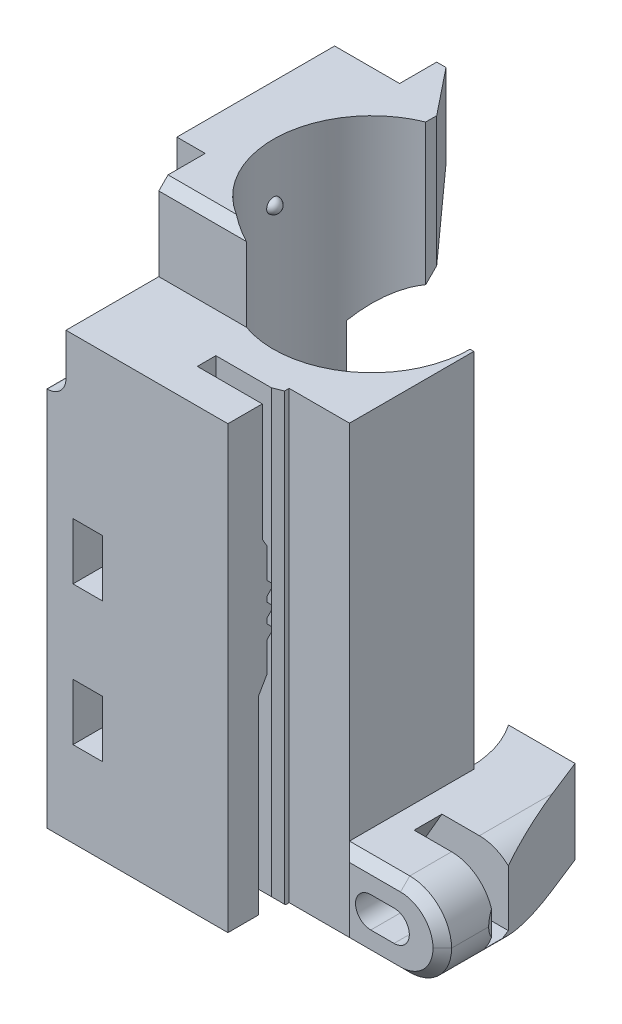
SolidWorks part; units mm, degrees
material "Custom Plastic"
ref_plane "Front Plane" through (0, 0, 0) normal (0, 0, 1) x (1, 0, 0)
ref_plane "Top Plane" through (0, 0, 0) normal (0, 1, 0) x (1, 0, 0)
ref_plane "Right Plane" through (0, 0, 0) normal (1, 0, 0) x (0, 0, -1)
sketch "Sketch2" plane through (0, 0, 0) normal (0, 1, 0) x (1, 0, 0)
  line L0 (22, -14.4) -> (22, -9.4)
  line L1 (16, 6) -> (16, -12.9) construction
  line L2 (11, -13.4) -> (4.5, -13.4)
  line L3 (4.5, -13.4) -> (4.5, -20)
  line L4 (4.5, -20) -> (-15, -20)
  line L5 (-15, -20) -> (-15, 16)
  line L6 (22, -9.4) -> (14.1647, -9.4) construction
  line L7 (8.7384, 6) -> (15.906, 6)
  line L8 (-15, 16) -> (-4, 16)
  line L9 (-4, 16) -> (-4, 9.8163)
  line L10 (11, -13.4) -> (12, -14.4)
  line L11 (12, -14.4) -> (22, -14.4)
  line L12 (22, -9.4) -> (15.906, 6)
  circle A0 centre (0, 0) radius 10.5 construction
  arc A1 (-4, 9.8163) -> (8.7384, 6) centre (0, 0) ccw
  arc A3 (14.1647, -9.4) -> (15.906, 6) centre (0, 0) ccw construction
  dimension "D1" = 21
  dimension "D2" = 0.1
  dimension "D11" = 17
  dimension "D3" = 4.5
  dimension "D4" = 16
  dimension "D5" = 15
  dimension "D6" = 13.4
  dimension "D7" = 20
  dimension "D8" = 16
  dimension "D9" = 4
  dimension "D10" = 6
  dimension "D12" = 22
  dimension "D14" = 45
  dimension "D15" = 11
  dimension "D16" = 1
extrude "Boss-Extrude1" add sketch "Sketch2" along normal blind 37 and the other way blind 20
sketch "Sketch3" plane through (0, 0, 0) normal (0, -1, 0) x (1, 0, 0)
  circle A0 centre (0, 0) radius 10.5
  dimension "D1" = 21
extrude "Cut-Extrude1" [suppressed] cut sketch "Sketch3" against normal blind 20 from offset 4 offset against normal yes
mirror "Mirror1" [suppressed] about plane through (0, 0, 0) normal (0, 1, 0)
sketch "Sketch4" plane through (0, 37, 0) normal (0, -1, 0) x (1, 0, 0)
  line L0 (4.5, 20) -> (4.5, 13.4) construction
  line L1 (-15, 20) -> (4.5, 20)
  line L2 (-15, 20) -> (-15, 9.9962)
  line L3 (-15, 9.9962) -> (4.5, 9.9962)
  line L4 (4.5, 20) -> (4.5, 9.9962)
extrude "Cut-Extrude3" [suppressed] cut sketch "Sketch4" along normal blind 11
sketch "Sketch5" plane through (4.5, 0, 0) normal (1, 0, 0) x (0, 0, -1)
  line L0 (-15.8, 5.718) -> (-15.3, 6.218)
  line L1 (-14.3, -20) -> (-16.3, -20)
  line L2 (-14.3, -20) -> (-14.3, 37)
  line L3 (-16.3, 37) -> (-14.3, 37)
  line L4 (-15.8, 2.5) -> (-15.8, 5.718)
  line L5 (-15.3, 6.218) -> (-15.3, 6.718)
  line L6 (-15.3, 6.718) -> (-15.8, 7.218)
  line L7 (-15.8, 9.782) -> (-15.3, 10.282)
  line L8 (-15.3, 10.282) -> (-15.3, 10.782)
  line L9 (-15.3, 10.782) -> (-15.8, 11.282)
  line L10 (-15.8, 7.75) -> (-15.3, 8.25)
  line L11 (-15.3, 8.25) -> (-15.3, 8.75)
  line L12 (-15.3, 8.75) -> (-15.8, 9.25)
  line L13 (-15.8, 9.25) -> (-15.8, 9.782)
  line L14 (-15.8, 2.5) -> (-16.3, 1.634)
  line L15 (-15.8, 7.218) -> (-15.8, 7.75)
  line L16 (-16.3, 1.634) -> (-16.3, -20)
  line L17 (-15.8, 11.282) -> (-15.8, 14.5)
  line L18 (-15.8, 14.5) -> (-16.3, 15.366)
  line L19 (-20, -20) -> (-13.4, -20) construction
  line L20 (16, 8.5) -> (-15.3, 8.5) construction
  line L21 (-16.3, 15.366) -> (-16.3, 37)
  line L22 (-20, 37) -> (-13.4, 37) construction
  line L23 (16, -20) -> (16, 37) construction
  dimension "D1" = 0.5
  dimension "D2" = 0.5
  dimension "D3" = 2.032
  dimension "D4" = 1.5
  dimension "D5" = 2
  dimension "D6" = 14.3
  dimension "D7" = 6
  dimension "D8" = 150
extrude "Cut-Extrude5" cut sketch "Sketch5" against normal blind 7
chamfer "Chamfer1" [suppressed] distance 1.2 angle 45
chamfer "Chamfer3" distance 0.5 angle 45 9 edges at (1, -20, 14.3) (-3.0421, -20, 10.1541) (-4, -20, -12.9082) (-9.5, -20, -16) (-15, -20, 2) (-5.25, -20, 20) (4.5, -20, 18.15) (1, -20, 16.3) (-2.5, -20, 15.3)
sketch "Sketch6" plane through (-15, 0, 0) normal (-1, 0, 0) x (0, 0, 1)
  line L0 (13, 7.5) -> (13, -7.5) construction
  line L1 (0, 0) -> (13, 0) construction
  circle A0 centre (13, 7.5) radius 1.55
  circle A1 centre (13, -7.5) radius 1.55
  dimension "D2" = 3.1
  dimension "D1" = 15
  dimension "D3" = 13
extrude "Cut-Extrude6" cut sketch "Sketch6" against normal blind 10
sketch "Sketch7" plane through (-15, 0, 0) normal (-1, 0, 0) x (0, 0, 1)
  line L0 (21.3141, -4.2) -> (21.3141, -10.3)
  line L1 (9.3668, -7.5) -> (10.9834, -10.3)
  line L2 (10.9834, -10.3) -> (21.3141, -10.3)
  line L3 (11.3834, 4.7) -> (9.7668, 7.5)
  line L4 (21.3141, 4.7) -> (11.3834, 4.7)
  line L5 (21.3141, -4.7) -> (11.3834, -4.7) construction
  line L6 (11.2721, -4.2) -> (9.3668, -7.5)
  line L7 (-3, 8.5) -> (19.4531, 8.5) construction
  line L8 (11.2721, -4.2) -> (21.3141, -4.2)
  line L9 (11.3834, 10.3) -> (21.7141, 10.3) construction
  line L10 (13.1374, -12.1691) -> (15.0359, -8.8809) construction
  line L11 (16.6078, -8.8418) -> (15.5516, -7.0123) construction
  line L12 (9.7668, 7.5) -> (11.6721, 10.8)
  line L13 (21.3141, 4.7) -> (21.3141, 10.8)
  line L14 (11.6721, 10.8) -> (21.3141, 10.8)
  circle A0 centre (12.6, -7.5) radius 2.8 construction
  circle A2 centre (13, 7.5) radius 2.8 construction
  circle A3 centre (13, 7.5) radius 1.55 construction
  point P4 (13, -7.5)
  dimension "D1" = 5.6
  dimension "D2" = 0.4
  dimension "D3" = 0.5
  dimension "D4" = 0.5
extrude "Cut-Extrude7" cut sketch "Sketch7" against normal blind 3.2 from offset 2.8 offset against normal yes
sketch "Sketch9" plane through (-15, 0, 0) normal (-1, 0, 0) x (0, 0, 1)
  line L0 (-16, 28) -> (-6, 18)
  line L1 (-16, -19.5) -> (-16, 37) construction
  line L2 (-6, 18) -> (-6, -20)
  line L3 (-16, -20) -> (20, -20) construction
  line L4 (-6, -20) -> (-16, -20)
  line L5 (-16, -20) -> (-16, 28)
  line L6 (-16, 37) -> (20, 37) construction
  dimension "D1" = 9
  dimension "D2" = 6
  dimension "D3" = 45
extrude "Cut-Extrude9" cut sketch "Sketch9" against normal blind 12 and the other way blind 10
sketch "Sketch12" plane through (-15, 0, 0) normal (-1, 0, 0) x (0, 0, 1)
  line L0 (8, 37) -> (8, 30)
  line L1 (-16, 37) -> (20, 37) construction
  line L2 (5, 25) -> (-13, 25)
  line L3 (-16, 28) -> (-13, 25)
  line L4 (-16, 28) -> (-6, 18) construction
  line L5 (-16, 28) -> (-16, 37)
  line L6 (-16, 37) -> (8, 37)
  line L7 (8, 30) -> (5, 30)
  line L8 (5, 30) -> (5, 25)
  dimension "D1" = 24
  dimension "D2" = 12
  dimension "D3" = 3
  dimension "D4" = 5
extrude "Boss-Extrude2" add sketch "Sketch12" along normal blind 1
sketch "Sketch10" plane through (0, 0, -16) normal (0, 0, -1) x (-1, 0, 0)
  line L1 (16, 37) -> (9, 37)
  line L2 (16, 37) -> (16, 28.8)
  line L3 (16, 28.8) -> (9, 28.8)
  line L4 (9, 37) -> (9, 28.8)
  line L5 (16, 37) -> (16, 28) construction
  line L6 (4, 28) -> (16, 28) construction
  line L7 (4, 37) -> (16, 37) construction
  dimension "D1" = 7
  dimension "D3" = 0.8
extrude "Cut-Extrude10" cut sketch "Sketch10" against normal blind 4
sketch "Sketch11" plane through (-16, 0, 0) normal (-1, 0, 0) x (0, 0, 1)
  line L0 (-12, 28.8) -> (-16, 28.8) construction
  line L2 (-16, 28) -> (-16, 28.8) construction
  circle A0 centre (-9, 26.3) radius 1.25
  circle A1 centre (1, 26.3) radius 1.25
  dimension "D3" = 10
  dimension "D4" = 2.5
  dimension "D1" = 2.5
  dimension "D2" = 7
extrude "Cut-Extrude11" cut sketch "Sketch11" against normal blind 4
chamfer "Chamfer4" distance 3 angle 45 2 edges
sketch "Sketch13" plane through (0, 37, 0) normal (0, 1, 0) x (1, 0, 0)
  line L0 (-16, -10) -> (0, -10)
  line L1 (0, -10) -> (0, 6.4112)
  line L2 (-16, -10) -> (-16, -20)
  line L3 (12, -20) -> (-16, -20)
  line L4 (0, 6.4112) -> (12, 6.4112)
  line L5 (12, -20) -> (12, 6.4112)
  line L7 (-15, -20) -> (4.5, -20) construction
extrude "Cut-Extrude12" cut sketch "Sketch13" against normal blind 9
chamfer "Chamfer5" distance 1 angle 45 1 edges at (-9.7578, 37, 10)
sketch "Sketch15" plane through (0, -20, -7.1) normal (0, 1, 0) x (1, 0, 0)
  line L1 (22, -21.5) -> (11, -21.5)
  line L2 (22, -21.5) -> (22, -1.1)
  line L3 (22, -1.1) -> (8.1933, -1.1)
  line L4 (11, -21.5) -> (11, -7.1)
  line L5 (11, -7.1) -> (8.1933, -7.1)
  line L6 (8.1933, -7.1) -> (8.1933, -1.1)
  dimension "D1" = 11
extrude "Cut-Extrude14" cut sketch "Sketch15" along normal through all from offset 9
chamfer "Chamfer6" distance 1 angle 45 1 edges at (-15, -0.75, -6)
chamfer "Chamfer7" distance 0.4 distance2 1 1 edges at (4.5, 4.25, 14.3) first distance on face at (4.5, -0.7, 13.84)
chamfer "Chamfer10" distance 0.4 distance2 2 1 edges at (4.5, -8.933, 16.3) first distance on face at (4.5, 7.65, 16.17)
sketch "Sketch17" plane through (0, 0, 14.4) normal (0, 0, 1) x (1, 0, 0)
  line L0 (15.55, -15.5) -> (22, -15.5) construction
  line L1 (22, -20) -> (22, -11) construction
  line L2 (14.3, -15.5) -> (16.8, -15.5) construction
  line L3 (14.3, -13.85) -> (16.8, -13.85)
  line L4 (14.3, -17.15) -> (16.8, -17.15)
  circle A0 centre (15.55, -15.5) radius 4.5 construction
  arc A1 (14.3, -13.85) -> (14.3, -17.15) centre (14.3, -15.5) ccw
  arc A2 (16.8, -17.15) -> (16.8, -13.85) centre (16.8, -15.5) ccw
  point P2 (11.05, -15.5)
  point P9 (15.55, -15.5)
  dimension "D2" = 9
  dimension "D3" = 1.65
  dimension "D1" = 11.05
  dimension "D4" = 2.5
extrude "Cut-Extrude16" cut sketch "Sketch17" against normal blind 6
fillet "Fillet2" radius 4.5 2 edges at (22, -11, 11.9) (22, -20, 11.9)
sketch "Sketch18" plane through (0, 0, 14.4) normal (0, 0, -1) x (-1, 0, 0)
  line L0 (-22.7084, -8.1113) -> (-22.7084, -18.3)
  line L1 (-10.8668, -15.5) -> (-15.1327, -8.1113)
  line L3 (-22.7084, -8.1113) -> (-15.1327, -8.1113)
  line L5 (-22.7084, -18.3) -> (-12.4834, -18.3)
  line L6 (-12.4834, -18.3) -> (-10.8668, -15.5)
  line L9 (-16.4286, -13.9332) -> (-17.2368, -15.3332) construction
  line L10 (-17.3332, -15.5) -> (-15.3536, -18.9286) construction
  line L11 (-12.4834, -12.7) -> (-14.1, -12.7) [skipped]
  circle A0 centre (-14.1, -15.5) radius 2.8 construction
  arc A3 (-14.3, -17.15) -> (-14.3, -13.85) centre (-14.3, -15.5) ccw construction
  point P10 (-14.3, -15.5)
  dimension "D2" = 5.6
  dimension "D1" = 0.2
extrude "Cut-Extrude17" cut sketch "Sketch18" against normal blind 0.5 and the other way blind 2.5 from offset 6
chamfer "Chamfer14" distance 1 angle 45 4 edges at (14.75, -11, 14.4) (20.682, -12.318, 14.4) (20.682, -18.682, 14.4) (14.75, -20, 14.4)
sketch "Sketch19" plane through (0, 0, 20) normal (0, 0, 1) x (1, 0, 0)
  line L0 (-16, 37) -> (-12.95, 37)
  line L1 (-12.95, 37) -> (-12.95, 23.5001)
  line L2 (-14.95, 21.5001) -> (-16, 21.5001)
  line L4 (-16, 37) -> (-5.6, 37) construction
  line L6 (-15, 28) -> (4.5, 28) construction
  line L8 (-16, 37) -> (-16, 21.5001)
  line L10 (-15, -19.5) -> (-15, 28) construction
  line L12 (-16, 33.5678) -> (-13.6361, 31.5078) construction
  line L13 (-16, 30) -> (-16, 36) construction
  arc A0 (-12.95, 30) -> (-13.6361, 31.5078) centre (-14.95, 30) ccw construction
  arc A1 (-14.95, 21.5001) -> (-12.95, 23.5001) centre (-14.95, 23.5001) ccw
  dimension "D1" = 4
  dimension "D2" = 2.05
  dimension "D3" = 2
extrude "Cut-Extrude18" cut sketch "Sketch19" against normal blind 15
chamfer "Chamfer15" distance 4 distance2 5 1 edges at (-4, 32.5, -16) first distance on face at (-9.6667, 31.2667, -16)
sketch "Sketch20" plane through (0, 0, 0) normal (0, 0, 1) x (1, 0, 0)
  line L1 (-10.6, 30.85) -> (-10.6, -13.85) construction
  line L2 (-10.6, 4.25) -> (4.5, 4.25) construction
  line L3 (4.5, -19.5) -> (4.5, 28) construction
  line L4 (-10.6, 30.1) -> (-10.6, 31.6)
  line L5 (-10.6, -13.1) -> (-10.6, -14.6)
  line L6 (4, -20) -> (-14.5, -20) construction
  arc A0 (-10.6, 31.6) -> (-10.6, 30.1) centre (-10.6, 30.85) ccw
  arc A1 (-10.6, -13.1) -> (-10.6, -14.6) centre (-10.6, -13.85) ccw
  dimension "D2" = 1.5
  dimension "D3" = 6.15
  dimension "D1" = 44.7
revolve "Revolve2" add sketch "Sketch20" angle 360 about L1
ref_axis "Axis1" through (0, -19.5, 0) along (0, 1, 0)
equation "\"y-plate-thickness\"=5"
equation "\"bed-plate-thickness\"=3"
equation "\"x-plate-thickness\"=5"
equation "\"rod-diameter\"=12"
equation "\"D1@Sketch15\"=\"rod-diameter\"/2+\"x-plate-thickness\""
